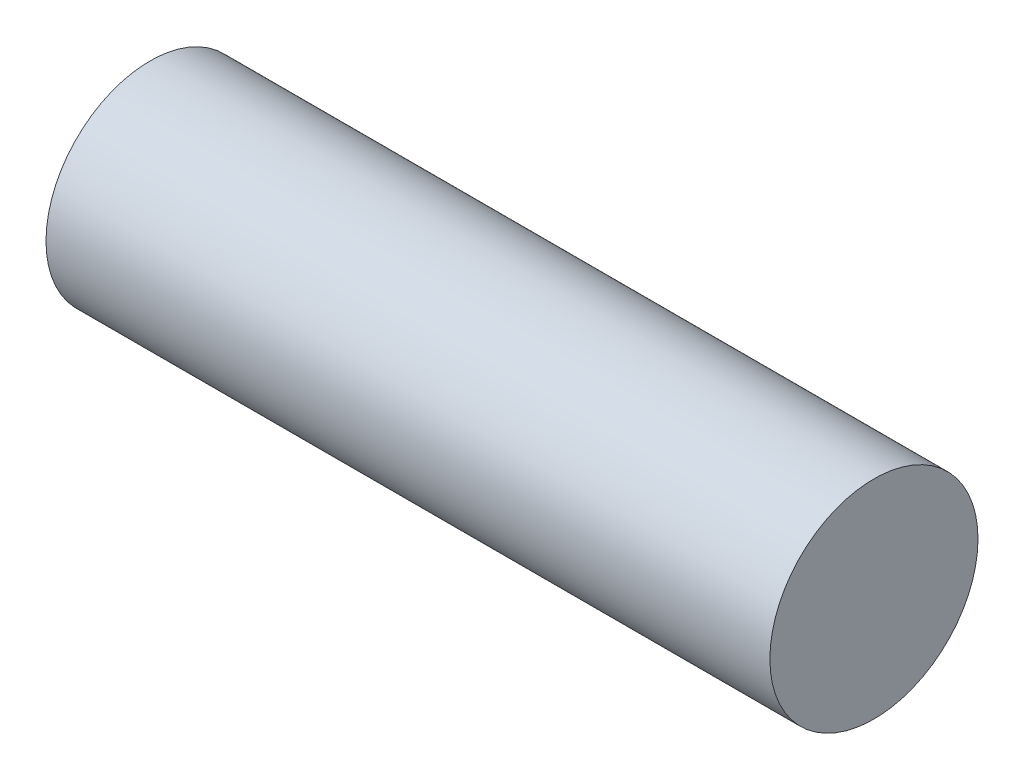
SolidWorks part; units mm, degrees
ref_plane "Front Plane" through (0, 0, 0) normal (0, 0, 1) x (1, 0, 0)
ref_plane "Top Plane" through (0, 0, 0) normal (0, 1, 0) x (1, 0, 0)
ref_plane "Right Plane" through (0, 0, 0) normal (1, 0, 0) x (0, 0, -1)
sketch "Sketch1" plane through (0, 0, 0) normal (1, 0, 0) x (0, 0, -1)
  circle A0 centre (0, 0) radius 5.75
  dimension "D1" = 11.5
extrude "Boss-Extrude1" add sketch "Sketch1" along normal blind 40
